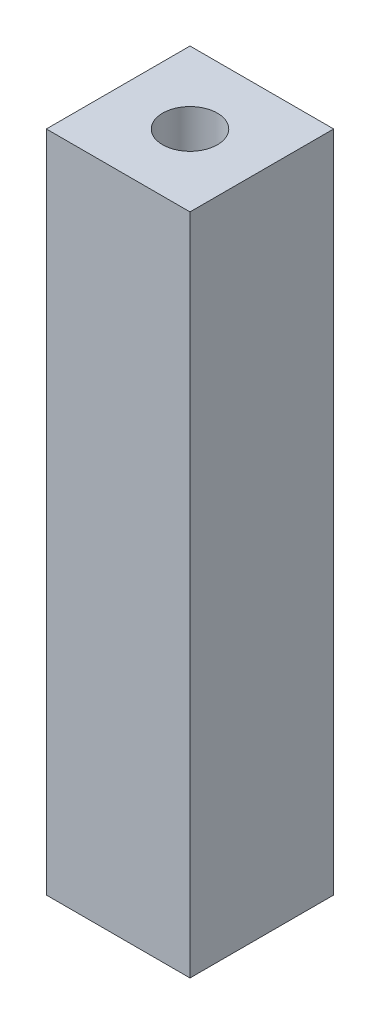
SolidWorks part; units mm, degrees
ref_plane "Front Plane" through (0, 0, 0) normal (0, 0, 1) x (1, 0, 0)
ref_plane "Top Plane" through (0, 0, 0) normal (0, 1, 0) x (1, 0, 0)
ref_plane "Right Plane" through (0, 0, 0) normal (1, 0, 0) x (0, 0, -1)
sketch "Sketch1" plane through (0, 0, 0) normal (0, 1, 0) x (1, 0, 0)
  line L1 (-5.5, 5.5) -> (5.5, 5.5)
  line L2 (-5.5, 5.5) -> (-5.5, -5.5)
  line L3 (-5.5, -5.5) -> (5.5, -5.5)
  line L4 (5.5, 5.5) -> (5.5, -5.5)
  line L5 (-5.5, 5.5) -> (5.5, -5.5) construction
  line L6 (-5.5, -5.5) -> (5.5, 5.5) construction
  point P0 (0, 0)
  dimension "D1" = 11
extrude "Boss-Extrude1" add sketch "Sketch1" along normal blind 50.8
hole_wizard "M5x0.8 Tapped Hole1" positions "Sketch2" profile "Sketch3" tap size "M5x0.8" standard "ANSI Metric" end condition through all
sketch "Sketch2" plane through (0, 50.8, 0) normal (0, 1, 0) x (1, 0, 0)
  point P0 (0, 0)
sketch "Sketch3" plane through (0, 50.8, 0) normal (1, 0, 0) x (0, 0, 1)
  line L0 (0, 0) -> (0, 50.8)
  line L1 (0, 50.8) -> (2.1, 50.8)
  line L2 (2.1, 50.8) -> (2.1, 0)
  line L5 (2.1, 0) -> (0, 0)
  line L11 (0, -6.35) -> (0, 107.95) construction
  dimension "Thru Tap Drill Dia." = 4.2
  dimension "Thru Tap Drill Depth" = 50.8
cosmetic thread "Hole Thread1" parameters "D2"=5
